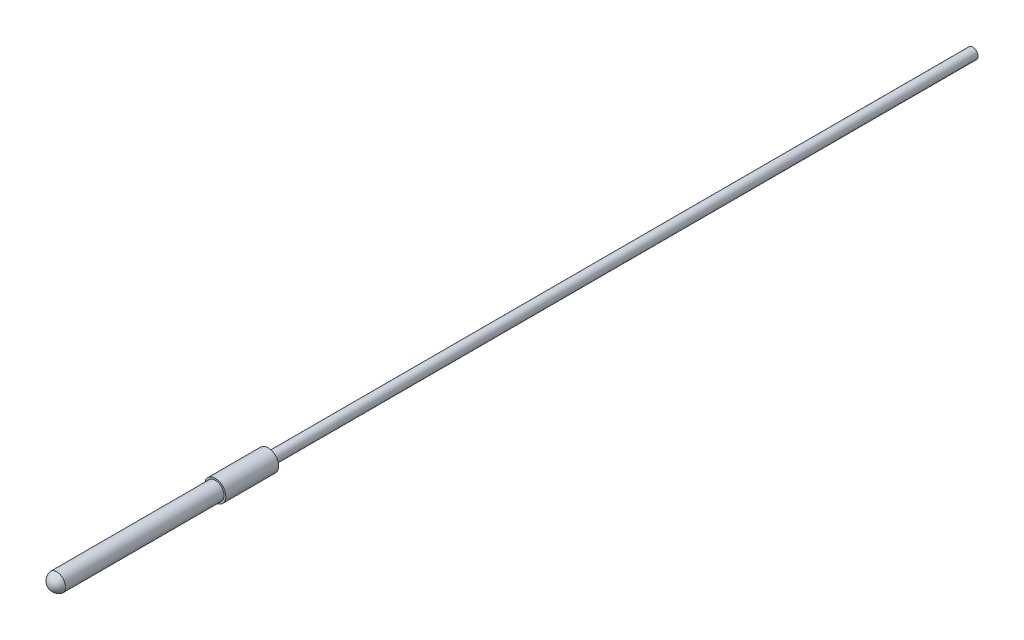
SolidWorks part; units mm, degrees
material "AISI 304"
ref_plane "Plan de face" through (0, 0, 0) normal (0, 0, 1) x (1, 0, 0)
ref_plane "Plan de dessus" through (0, 0, 0) normal (0, 1, 0) x (1, 0, 0)
ref_plane "Plan de droite" through (0, 0, 0) normal (1, 0, 0) x (0, 0, -1)
sketch "Esquisse1" plane through (0, 0, 0) normal (0, 0, 1) x (1, 0, 0)
  circle A0 centre (0, 0) radius 2.5
  dimension "D1" = 5
extrude "Boss.-Extru.1" add sketch "Esquisse1" along normal blind 45
dome "Dôme1" faces to dome 1 distance 2 reverse direction no elliptical dome no face at (2.5, 0, 45) parameters "D1"=2
sketch "Esquisse2" plane through (0, 0, 0) normal (0, 0, -1) x (-1, 0, 0)
  circle A0 centre (0, 0) radius 3
  dimension "D1" = 6
extrude "Boss.-Extru.2" add sketch "Esquisse2" along normal blind 15
sketch "Esquisse3" plane through (0, 0, -15) normal (0, 0, -1) x (-1, 0, 0)
  circle A0 centre (0, 0) radius 1.5
  dimension "D1" = 3
extrude "Boss.-Extru.3" add sketch "Esquisse3" along normal blind 200
